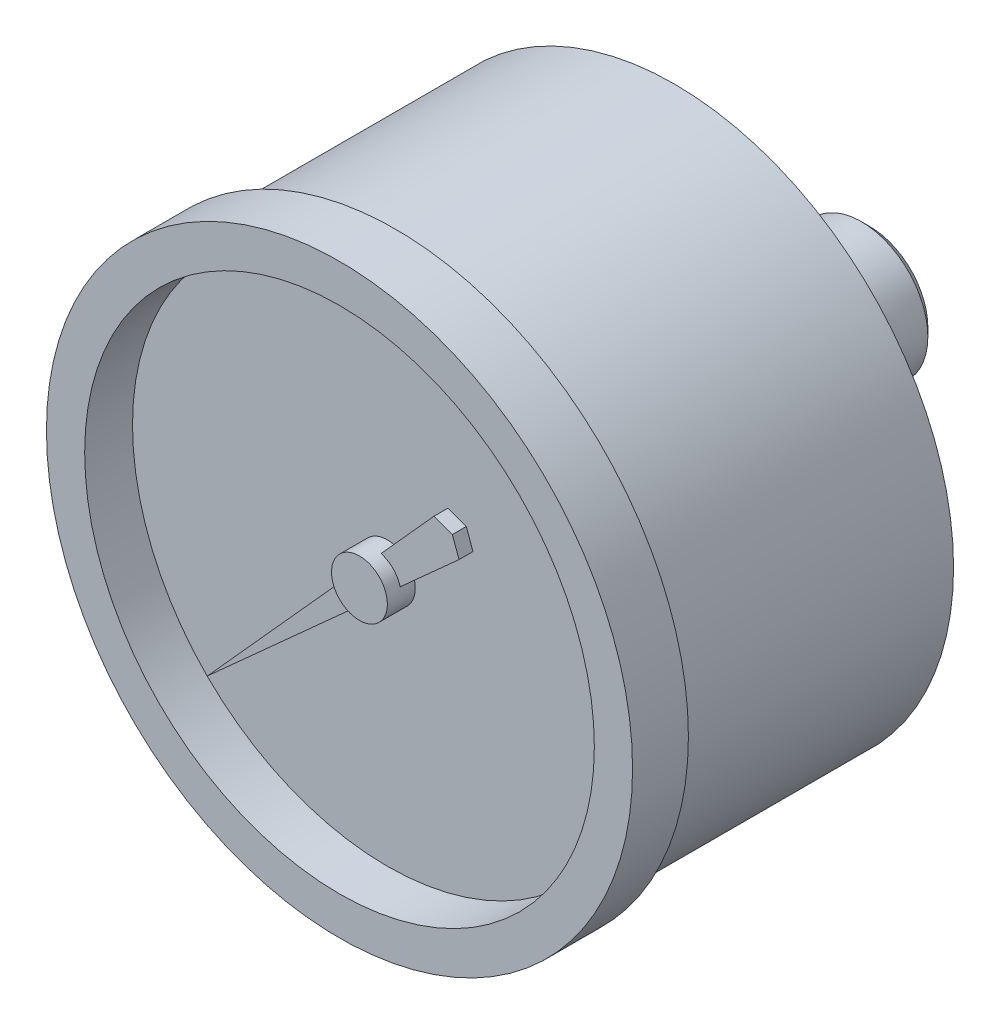
SolidWorks part; units mm, degrees
ref_plane "前视基准面" through (0, 0, 0) normal (0, 0, 1) x (1, 0, 0)
ref_plane "上视基准面" through (0, 0, 0) normal (0, 1, 0) x (1, 0, 0)
ref_plane "右视基准面" through (0, 0, 0) normal (1, 0, 0) x (0, 0, -1)
sketch "草图1" plane through (0, 0, 0) normal (1, 0, 0) x (0, 0, -1)
  line L0 (-34.5714, 0) -> (-34.5714, 18.2609)
  line L1 (-34.5714, 18.2609) -> (-38, 18.2609)
  line L2 (-38, 18.2609) -> (-38, 21)
  line L3 (-38, 21) -> (-34, 21)
  line L4 (-34, 21) -> (-34, 20)
  line L5 (-34, 20) -> (-14, 20)
  line L6 (-14, 20) -> (-14, 7.5862)
  line L7 (-14, 7.5862) -> (-8.4, 7.5862)
  line L8 (-8.4, 7.5862) -> (-8.4, 5.0015)
  line L9 (-8.4, 5.0015) -> (-0.6, 4.7577)
  line L10 (-0.6, 4.7577) -> (0, 4.1577)
  line L11 (0, 4.1577) -> (0, 0)
  line L12 (0, 0) -> (-34.5714, 0)
  line L13 (0, 0) -> (-38, 0) construction
revolve "旋转1" add sketch "草图1" angle 360 about L13 reverse direction yes
ref_plane "基准面4" through (0, 0, 34.5714) normal (0, 0, 1) x (1, 0, 0)
sketch "草图2" plane through (0, 0, 34.5714) normal (0, 0, 1) x (1, 0, 0)
  line L0 (-11.8794, -11.8794) -> (6.1356, 4.3414)
  line L1 (6.1356, 4.3414) -> (5.6569, 5.6569)
  line L2 (5.6569, 5.6569) -> (4.3414, 6.1356)
  line L3 (4.3414, 6.1356) -> (-11.8794, -11.8794)
extrude "凸台-拉伸1" add sketch "草图2" along normal blind 1
sketch "草图3" plane through (0, 0, 34.5714) normal (0, 0, 1) x (1, 0, 0)
  circle A0 centre (0, 0) radius 2
extrude "凸台-拉伸2" add sketch "草图3" along normal blind 2
sketch "草图4" plane through (0, 0, 0) normal (0, 0, 1) x (1, 0, 0)
  line L0 (-19.6069, -23.6057) -> (17.285, -23.6057)
  line L1 (17.285, -23.6057) -> (17.285, 20.5098)
  line L2 (17.285, 20.5098) -> (-19.6069, 20.5098)
  line L3 (-19.6069, 20.5098) -> (-19.6069, -23.6057)
  line L4 (-5.5, -5.5) -> (5.5, -5.5)
  line L5 (5.5, -5.5) -> (5.5, 5.5)
  line L6 (5.5, 5.5) -> (-5.5, 5.5)
  line L7 (-5.5, 5.5) -> (-5.5, -5.5)
extrude "切除-拉伸1" cut sketch "草图4" along normal blind 14
ref_plane "gage XY" through (0, 0, 0) normal (0, 0, 1) x (1, 0, 0)
ref_plane "gage XZ" through (0, 0, 0) normal (0, -1, 0) x (-1, 0, 0)
ref_plane "gage YZ" through (0, 0, 0) normal (1, 0, 0) x (0, 0, -1)
ref_axis "gage X" through (-80.9, 0, 0) along (1, 0, 0)
ref_axis "gage Y" through (0, -50, 0) along (0, 1, 0)
ref_axis "gage Z" through (0, 0, 80.9) along (0, 0, -1)
sketch3d "gage"
  point P0 (0, 0, 0)
